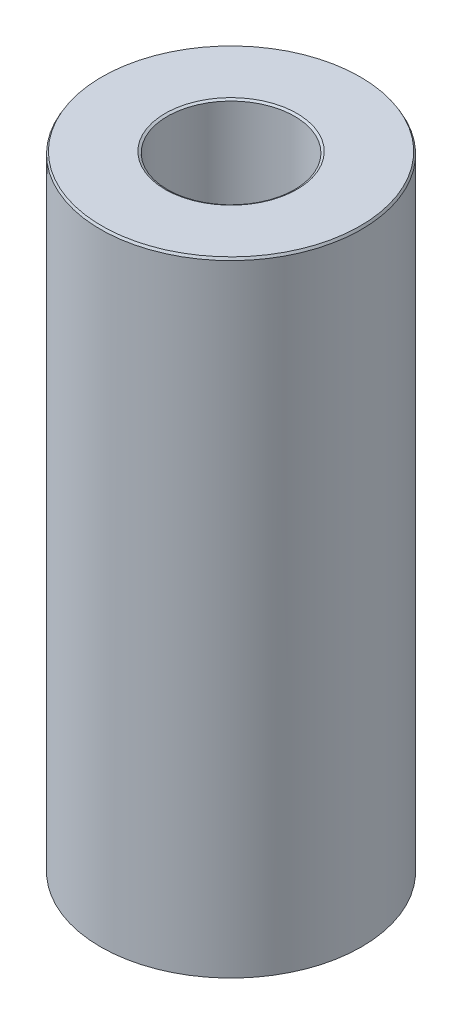
SolidWorks part; units mm, degrees
ref_plane "Front Plane" through (0, 0, 0) normal (0, 0, 1) x (1, 0, 0)
ref_plane "Top Plane" through (0, 0, 0) normal (0, 1, 0) x (1, 0, 0)
ref_plane "Right Plane" through (0, 0, 0) normal (1, 0, 0) x (0, 0, -1)
sketch "Sketch1" plane through (0, 0, 0) normal (0, 1, 0) x (1, 0, 0)
  circle A0 centre (0, 0) radius 52.5
  dimension "SLEEVE_OD" = 105
extrude "Boss-Extrude1" add sketch "Sketch1" along normal blind 251.4293
sketch "Sketch2" plane through (0, 0, 0) normal (0, 1, 0) x (1, 0, 0)
  circle A0 centre (0, 0) radius 25.5784
  dimension "BORE_D" = 51.1568
extrude "Cut-Extrude1" cut sketch "Sketch2" along normal through all
chamfer "Chamfer1" distance 0.9324 angle 30 4 edges at (0, 251.4293, 25.5784) (0, 0, 25.5784) (0, 0, 52.5) (0, 251.4293, 52.5) first distance on face at (0, 251.4293, 25.5784) first distance on face at (0, 0, 25.5784) first distance on face at (0, 251.4293, 52.5)
